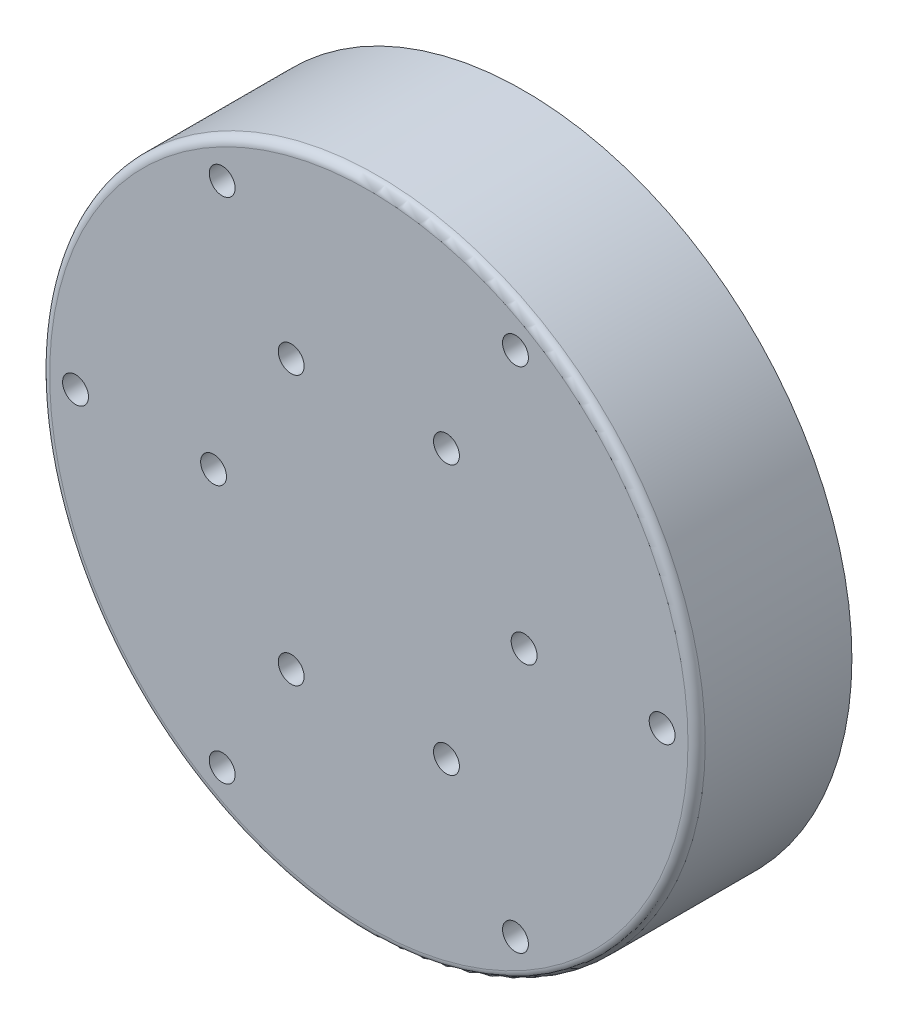
SolidWorks part; units mm, degrees
material "ABS"
ref_plane "Спереди" through (0, 0, 0) normal (0, 0, 1) x (1, 0, 0)
ref_plane "Сверху" through (0, 0, 0) normal (0, 1, 0) x (1, 0, 0)
ref_plane "Справа" through (0, 0, 0) normal (1, 0, 0) x (0, 0, -1)
other "Configuration Table"
sketch "Эскиз1" plane through (0, 0, 0) normal (0, 0, 1) x (1, 0, 0)
  circle A0 centre (0, 0) radius 38
  dimension "D1" = 76
extrude "Бобышка-Вытянуть1" add sketch "Эскиз1" along normal blind 18
sketch "Эскиз2" plane through (0, 0, 18) normal (0, 0, 1) x (1, 0, 0)
  line L0 (0, 0) -> (-34, 0) construction
  line L1 (0, 0) -> (-17, 29.4449) construction
  circle A0 centre (0, 0) radius 34 construction
  circle A1 centre (-34, 0) radius 1.5
  circle A2 centre (0, 0) radius 34 construction
  circle A3 centre (-17, 29.4449) radius 1.5
  circle A4 centre (0, 0) radius 34 construction
  circle A5 centre (17, 29.4449) radius 1.5
  circle A6 centre (0, 0) radius 34 construction
  circle A7 centre (34, 0) radius 1.5
  circle A8 centre (0, 0) radius 34 construction
  circle A9 centre (17, -29.4449) radius 1.5
  circle A10 centre (0, 0) radius 34 construction
  circle A11 centre (-17, -29.4449) radius 1.5
  dimension "D1" = 68
  dimension "D2" = 3
  dimension "D4" = 60
  dimension "D3" = 6
extrude "Вырез-Вытянуть1" cut sketch "Эскиз2" against normal up to next contours A7 | A5 | A3 | A1 | A11 | A9
sketch "Эскиз3" plane through (0, 0, 0) normal (0, 0, -1) x (-1, 0, 0)
  line L0 (-13.0767, -27) -> (13.0767, -27)
  arc A0 (13.0767, -27) -> (-13.0767, -27) centre (0, 0) ccw
  dimension "D1" = 60
  dimension "D2" = 27
extrude "Вырез-Вытянуть2" cut sketch "Эскиз3" against normal blind 12.5
fillet "Скругление1" radius 1 1 edges at (38, 0, 18)
ref_plane "Плоскость1" through (0, -27, 0) normal (0, 1, 0) x (1, 0, 0)
sketch "Эскиз6" plane through (0, -27, 0) normal (0, 1, 0) x (1, 0, 0)
  line L0 (38, 0) -> (-38, 0) construction
  line L1 (-10, -8.5) -> (10, -8.5)
  line L2 (-10, -8.5) -> (-10, -12.5)
  line L3 (-10, -12.5) -> (10, -12.5)
  line L4 (10, -8.5) -> (10, -12.5)
  line L5 (-10, -8.5) -> (10, -12.5) construction
  line L6 (-10, -12.5) -> (10, -8.5) construction
  line L7 (0, 24) -> (0, -24) construction
  point P0 (0, -10.5)
  point P11 (0, 0)
  dimension "D1" = 4
  dimension "D2" = 20
  dimension "D3" = 8.5
  dimension "D4" = 10
extrude "Вырез-Вытянуть7" cut sketch "Эскиз6" against normal up to next
sketch "Эскиз7" plane through (0, 0, 18) normal (0, 0, 1) x (1, 0, 0)
  line L0 (0, 0) -> (-18, 0) construction
  circle A1 centre (0, 0) radius 18 construction
  circle A2 centre (-18, 0) radius 1.5
  circle A4 centre (-9, 15.5885) radius 1.5
  circle A6 centre (9, 15.5885) radius 1.5
  circle A8 centre (18, 0) radius 1.5
  circle A10 centre (9, -15.5885) radius 1.5
  circle A12 centre (-9, -15.5885) radius 1.5
  circle A13 centre (0, 0) radius 18 [skipped]
  circle A14 centre (0, 0) radius 18 [skipped]
  circle A15 centre (0, 0) radius 18 [skipped]
  circle A16 centre (0, 0) radius 18 [skipped]
  circle A17 centre (0, 0) radius 18 [skipped]
  dimension "D3" = 6
  dimension "D1" = 36
  dimension "D2" = 3
extrude "Вырез-Вытянуть8" cut sketch "Эскиз7" against normal up to next
